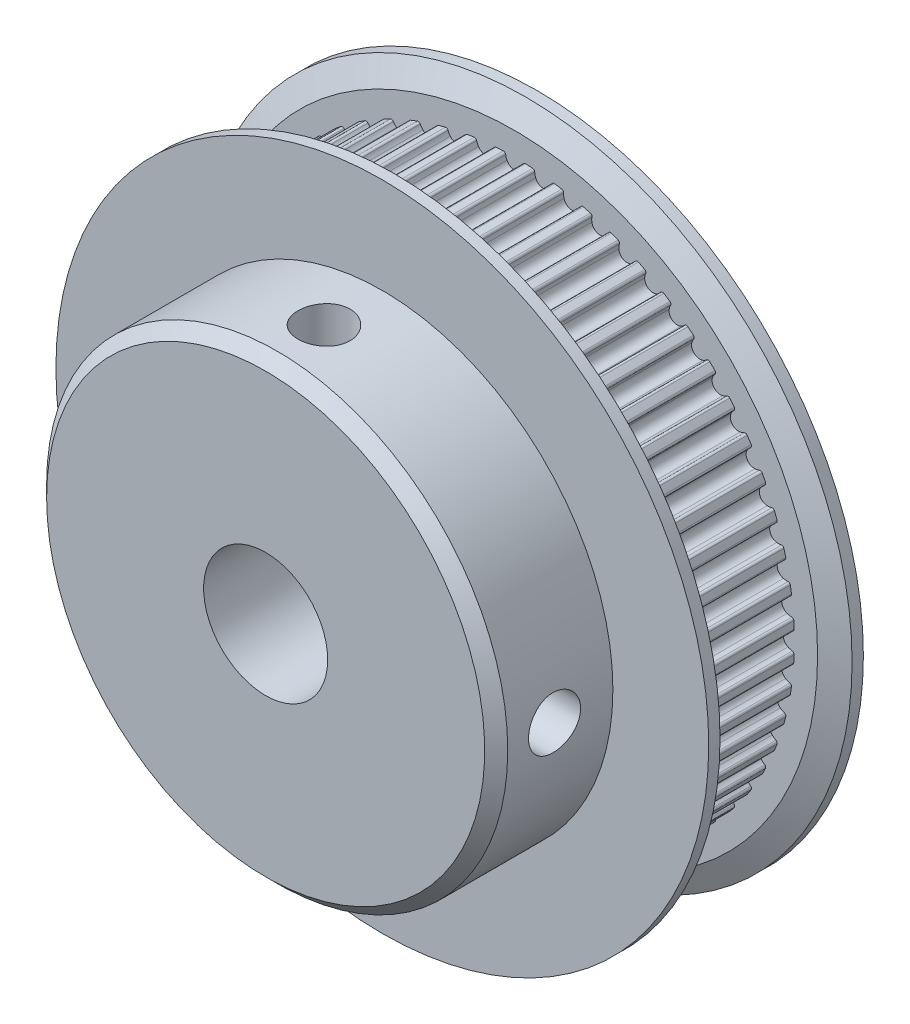
SolidWorks part; units mm, degrees
ref_plane "Front Plane" through (0, 0, 0) normal (0, 0, 1) x (1, 0, 0)
ref_plane "Top Plane" through (0, 0, 0) normal (0, 1, 0) x (1, 0, 0)
ref_plane "Right Plane" through (0, 0, 0) normal (1, 0, 0) x (0, 0, -1)
sketch "Sketch1" plane through (0, 0, 0) normal (0, 0, 1) x (1, 0, 0)
  line L1 (-1.9027, 18.097) -> (1.9027, 18.097) construction
  line L4 (0, 0) -> (0, 18.097) construction
  line L5 (0, 18.097) -> (0, 19.7033) construction
  line L6 (0, 19.101) -> (1.9973, 18.9963) construction
  line L7 (1.9973, 18.9963) -> (2.8966, 18.9017) construction
  line L8 (1.9973, 18.9963) -> (1.9027, 18.097) construction
  line L9 (-1.9973, 18.9963) -> (-1.9027, 18.097) construction
  line L10 (-1.9707, 18.7437) -> (-2.31, 21.971)
  line L11 (-2.31, 21.971) -> (2.31, 21.971)
  line L12 (2.31, 21.971) -> (1.9707, 18.7437)
  circle A0 centre (0, 0) radius 19.101 construction
  circle A1 centre (0, 0) radius 21.971 construction
  circle A2 centre (0, 0) radius 18.847 construction
  arc A3 (-0.4989, 18.4088) -> (0.4989, 18.4088) centre (0, 18.652) ccw
  arc A4 (-0.4989, 18.4088) -> (-0.5897, 18.7039) centre (0.4, 18.847) cw
  arc A5 (-1.9707, 18.7437) -> (-0.7441, 18.8323) centre (0, 0) cw
  arc A6 (-0.5897, 18.7039) -> (-0.7441, 18.8323) centre (-0.7382, 18.6824) ccw
  arc A7 (1.9707, 18.7437) -> (0.7441, 18.8323) centre (0, 0) ccw
  arc A8 (0.5897, 18.7039) -> (0.7441, 18.8323) centre (0.7382, 18.6824) cw
  arc A9 (0.4989, 18.4088) -> (0.5897, 18.7039) centre (-0.4, 18.847) ccw
  point P6 (0, 20.9083)
  point P11 (0, 19.101)
  point P13 (0, 21.971)
  point P14 (0, 18.847)
  dimension "D1" = 1.205
  dimension "D2" = 0.6023
sketch "Sketch2" plane through (0, 0, 0) normal (1, 0, 0) x (0, 0, -1)
  line L0 (-9.1313, 3.175) -> (9.1313, 3.175)
  line L1 (-9.1313, 3.175) -> (-9.1313, 15.52)
  line L2 (-9.1313, 15.52) -> (-1.2787, 15.52)
  line L3 (-1.2787, 15.52) -> (-1.2787, 21.971)
  line L4 (-1.2787, 21.971) -> (0.2413, 21.971) construction
  line L5 (0.2413, 21.971) -> (0.2413, 18.847) construction
  line L6 (0.2413, 18.847) -> (7.6113, 18.847)
  line L7 (7.6113, 18.847) -> (7.6113, 21.971) construction
  line L8 (7.6113, 21.971) -> (9.1313, 21.971) construction
  line L9 (9.1313, 21.971) -> (9.1313, 3.175)
  line L10 (-9.1313, 0) -> (9.1313, 0) construction
  line L11 (8.3713, 21.971) -> (7.6113, 20.409)
  line L12 (0.2413, 20.409) -> (-0.5187, 21.971)
  line L13 (-1.2787, 21.971) -> (-0.5187, 21.971)
  line L14 (0.2413, 20.409) -> (0.2413, 18.847)
  line L15 (7.6113, 18.847) -> (7.6113, 20.409)
  line L16 (8.3713, 21.971) -> (9.1313, 21.971)
  arc A0 (0.2413, 20.409) -> (-0.5187, 21.971) centre (-1.7439, 20.409) ccw construction
  arc A1 (7.6113, 20.409) -> (8.3713, 21.971) centre (9.5965, 20.409) cw construction
  point P12 (0.2413, 20.409)
  point P14 (-0.5187, 21.971)
  point P20 (7.6113, 20.409)
  point P21 (8.3713, 21.971)
  point P25 (7.6113, 0)
  point P26 (0.2413, 0)
revolve "Revolve1" add sketch "Sketch2" angle 360 mid plane about L10
sketch "Sketch3" plane through (0, 0, 0) normal (0, 0, 1) x (1, 0, 0)
  line L6 (2.31, 21.971) -> (-2.31, 21.971)
  line L7 (1.9707, 18.7437) -> (2.31, 21.971)
  line L8 (-2.31, 21.971) -> (-1.9707, 18.7437)
  line L9 (2.31, 21.971) -> (-2.31, 21.971)
  line L10 (1.9707, 18.7437) -> (2.31, 21.971)
  line L11 (-2.31, 21.971) -> (-1.9707, 18.7437)
  arc A8 (1.9707, 18.7437) -> (0.7441, 18.8323) centre (0, 0) ccw
  arc A9 (0.7441, 18.8323) -> (0.5897, 18.7039) centre (0.7382, 18.6824) ccw
  arc A10 (0.4989, 18.4088) -> (0.5897, 18.7039) centre (-0.4, 18.847) ccw
  arc A11 (-0.4989, 18.4088) -> (0.4989, 18.4088) centre (0, 18.652) ccw
  arc A12 (-0.5897, 18.7039) -> (-0.4989, 18.4088) centre (0.4, 18.847) ccw
  arc A13 (-0.5897, 18.7039) -> (-0.7441, 18.8323) centre (-0.7382, 18.6824) ccw
  arc A14 (-0.7441, 18.8323) -> (-1.9707, 18.7437) centre (0, 0) ccw
  arc A15 (1.9707, 18.7437) -> (0.7441, 18.8323) centre (0, 0) ccw
  arc A16 (0.7441, 18.8323) -> (0.5897, 18.7039) centre (0.7382, 18.6824) ccw
  arc A17 (0.4989, 18.4088) -> (0.5897, 18.7039) centre (-0.4, 18.847) ccw
  arc A18 (-0.4989, 18.4088) -> (0.4989, 18.4088) centre (0, 18.652) ccw
  arc A19 (-0.5897, 18.7039) -> (-0.4989, 18.4088) centre (0.4, 18.847) ccw
  arc A20 (-0.5897, 18.7039) -> (-0.7441, 18.8323) centre (-0.7382, 18.6824) ccw
  arc A21 (-0.7441, 18.8323) -> (-1.9707, 18.7437) centre (0, 0) ccw
  dimension "D1" = 0
extrude "Cut-Extrude1" cut sketch "Sketch3" against normal up to vertex (7.6113 mm away) from vertex up to point (0, 18.847, -7.6113) starting at point (0, 18.847, -0.2413)
pattern_circular "CirPattern1" count 60 over 360 about axis through (0, 0, 9.1313) along (0, 0, 1) of "Cut-Extrude1"
sketch "Sketch4" plane through (0, 0, 0) normal (1, 0, 0) x (0, -1, 0)
  line L0 (0, -1.2787) -> (0, -9.1313) construction
  line L1 (-15.52, -1.2787) -> (15.52, -1.2787) construction
  line L2 (-15.52, -9.1313) -> (15.52, -9.1313) construction
  circle A0 centre (0, -5.205) radius 1.7526
extrude "Cut-Extrude2" cut sketch "Sketch4" along normal through all
ref_plane "Plane1" through (0, 0, 5.205) normal (0, 0, 1) x (1, 0, 0)
sketch "Sketch5" plane through (0, 0, 5.205) normal (0, 0, 1) x (1, 0, 0)
  line L0 (0, 0.1664) -> (0, 15.52) construction
  line L1 (3.175, -1.3716) -> (3.175, 0)
  line L2 (3.556, -1.7526) -> (15.0397, -1.7526)
  line L3 (3.175, 0) -> (15.52, 0) construction
  line L4 (3.175, 0) -> (15.4207, 0)
  line L5 (15.4207, 0) -> (15.4207, -1.3716)
  line L6 (3.556, -1.7526) -> (3.175, -1.3716)
  line L7 (15.4207, -1.3716) -> (15.0397, -1.7526)
  circle A0 centre (0, 0) radius 15.52 construction
  circle A1 centre (0, 0) radius 3.175 construction
  point P2 (3.175, -1.7526)
  point P11 (15.4207, -1.7526)
revolve "Revolve2" [suppressed] add sketch "Sketch5" angle 360 mid plane about L4
sketch "Sketch6" [suppressed] plane through (15.4207, 5.3841, 0) normal (-1, 0, 0) x (0, -1, 0)
  line L1 (5.3841, 6.2169) -> (4.5078, 5.7109)
  line L2 (4.5078, 5.7109) -> (4.5078, 4.6991)
  line L3 (4.5078, 4.6991) -> (5.3841, 4.1931)
  line L4 (5.3841, 4.1931) -> (6.2604, 4.6991)
  line L5 (6.2604, 4.6991) -> (6.2604, 5.7109)
  line L6 (6.2604, 5.7109) -> (5.3841, 6.2169)
  circle A0 centre (5.3841, 5.205) radius 0.8763 construction
  dimension "D1" = 1.7526
extrude "Cut-Extrude3" [suppressed] cut sketch "Sketch6" along normal blind 1.3144
pattern_circular "CirPattern2" count 2 over 90 about axis through (0, 0, 9.1313) along (0, 0, 1) of "Cut-Extrude2", "Revolve2", "Cut-Extrude3"
chamfer "Chamfer1" distance 0.776 angle 45 2 edges at (3.175, 0, 9.1313) (15.52, 0, 9.1313)
ref_axis "Center Axis 1" through (0, 0, -9.1313) along (0, 0, 1)
ref_plane "Contact Plane 1" through (0, 0, 9.1313) normal (0, 0, 1) x (1, 0, 0)
ref_plane "Contact Plane 2" through (0, 0, -9.1313) normal (0, 0, -1) x (-1, 0, 0)
sketch "Sketch7" plane through (0, 0, 9.1313) normal (0, 0, 1) x (1, 0, 0)
  circle A0 centre (0, 0) radius 4.175
  dimension "D1" = 8.35
extrude "Cut-Extrude4" cut sketch "Sketch7" against normal through all
equation "\"D2@Sketch1\" = \"D1@Sketch1\"/2"
equation "\"D1@Sketch6\" = \"Set Screw@Sketch4\" / 2"
equation "\"D1@Cut-Extrude3\" = \"D1@Sketch6\"*.75"
equation "\"D1@Chamfer1\"=\"Hub Dia@Sketch2\"*.025"
